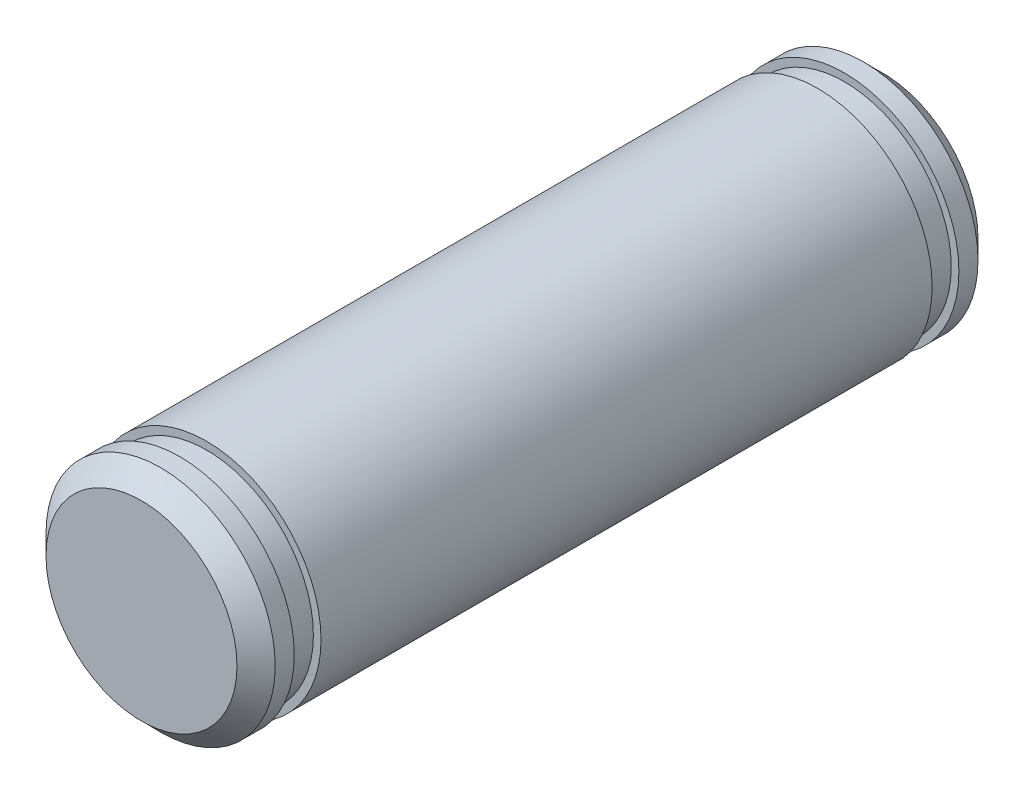
SolidWorks part; units mm, degrees
material "Chromowa stal nierdzewna"
ref_plane "Płaszczyzna przednia" through (0, 0, 0) normal (0, 0, 1) x (1, 0, 0)
ref_plane "Płaszczyzna górna" through (0, 0, 0) normal (0, 1, 0) x (1, 0, 0)
ref_plane "Płaszczyzna prawa" through (0, 0, 0) normal (1, 0, 0) x (0, 0, -1)
sketch "Szkic1" plane through (0, 0, 0) normal (0, 0, 1) x (1, 0, 0)
  circle A0 centre (0, 0) radius 3
  dimension "D1" = 6
extrude "Dodanie-wyciągnięcie1" add sketch "Szkic1" along normal blind 19.4
chamfer "Sfazowanie1" distance 0.5 angle 45 2 edges at (3, 0, 0) (3, 0, 19.4)
sketch "Szkic2" plane through (0, 0, 19.4) normal (0, 0, 1) x (1, 0, 0)
  circle A0 centre (0, 0) radius 3
  circle A1 centre (0, 0) radius 2.8
  dimension "D1" = 6
  dimension "D2" = 5.6
extrude "Wytnij-wyciągnięcie1" cut sketch "Szkic2" against normal blind 0.7 from offset 1 offset against normal yes
sketch "Szkic3" plane through (0, 0, 0) normal (0, 0, -1) x (-1, 0, 0)
  circle A0 centre (0, 0) radius 3
  circle A1 centre (0, 0) radius 2.8
  dimension "D1" = 6
  dimension "5,6" = 5.6
extrude "Wytnij-wyciągnięcie2" cut sketch "Szkic3" against normal blind 0.7 from offset 1 offset against normal yes
